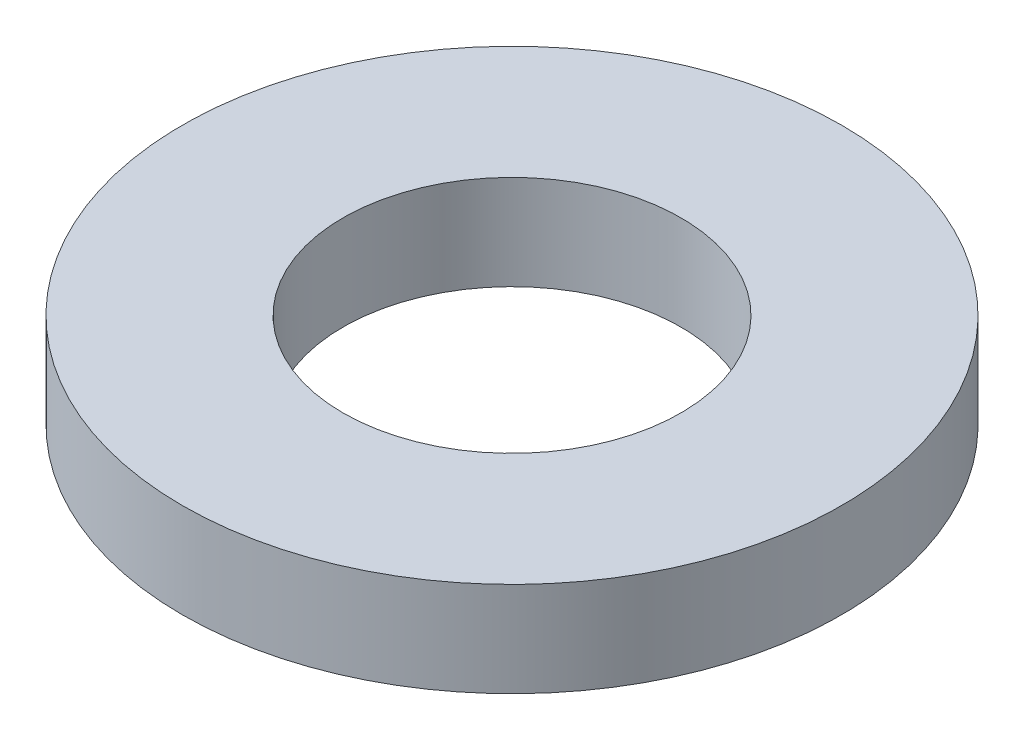
SolidWorks part; units mm, degrees
ref_plane "Front Plane" through (0, 0, 0) normal (0, 0, 1) x (1, 0, 0)
ref_plane "Top Plane" through (0, 0, 0) normal (0, 1, 0) x (1, 0, 0)
ref_plane "Right Plane" through (0, 0, 0) normal (1, 0, 0) x (0, 0, -1)
sketch "Sketch1" plane through (0, 0, 0) normal (0, 1, 0) x (1, 0, 0)
  circle A0 centre (0, 0) radius 97.5
  dimension "FLANGE_OD" = 195
extrude "Boss-Extrude1" add sketch "Sketch1" along normal blind 28
sketch "Sketch2" plane through (0, 0, 0) normal (0, 1, 0) x (1, 0, 0)
  circle A0 centre (0, 0) radius 50
  dimension "BORE_D" = 100
extrude "Cut-Extrude1" cut sketch "Sketch2" along normal through all
sketch "Sketch3" plane through (0, 28, 0) normal (0, 1, 0) x (1, 0, 0)
  circle A0 centre (0, 0) radius 40.2307 construction
  circle A1 centre (-40.2307, 0) radius 4.5731
  dimension "BOLT_D" = 9.1461
  dimension "BOLT_PCD" = 80.4613
extrude "Cut-Extrude2" cut sketch "Sketch3" against normal blind 27.4951 rebuild error yes
pattern_circular "CirPattern1" count 5 over 360 rebuild error yes
